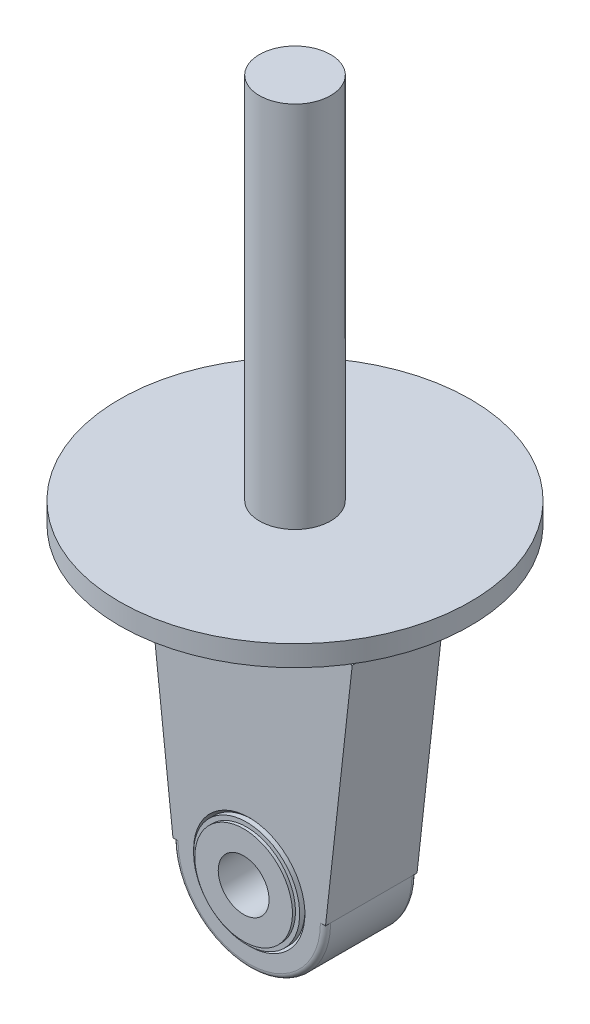
SolidWorks part; units mm, degrees
ref_plane "Front Plane" through (0, 0, 0) normal (0, 0, 1) x (1, 0, 0)
ref_plane "Top Plane" through (0, 0, 0) normal (0, 1, 0) x (1, 0, 0)
ref_plane "Right Plane" through (0, 0, 0) normal (1, 0, 0) x (0, 0, -1)
sketch "Sketch2" plane through (0, 0, 0) normal (0, 1, 0) x (1, 0, 0)
  line L0 (5, 10.1) -> (5, -10.1)
  line L1 (5, 10.1) -> (9.6, 10.1)
  line L2 (9.6, 10.1) -> (9.6, 9.5102)
  line L3 (9.6, 9.5102) -> (10.4331, 9.5102)
  line L4 (10.4331, 9.5102) -> (10.4331, 8.4874)
  line L5 (15, 8) -> (15, -8)
  line L6 (10.4331, 8.4874) -> (10.9456, 9)
  line L7 (0, 9.9454) -> (0, -9.3057) construction
  line L8 (-12.5165, 0) -> (17.2038, 0) construction
  line L9 (10.9456, 9) -> (14, 9)
  line L10 (10.9456, -9) -> (14, -9)
  line L11 (10.4331, -8.4874) -> (10.9456, -9)
  line L13 (10.4331, -9.5102) -> (10.4331, -8.4874)
  line L14 (9.6, -9.5102) -> (10.4331, -9.5102)
  line L15 (9.6, -10.1) -> (9.6, -9.5102)
  line L16 (5, -10.1) -> (9.6, -10.1)
  arc A0 (14, -9) -> (15, -8) centre (14, -8) ccw
  arc A1 (14, 9) -> (15, 8) centre (14, 8) cw
  point P2 (5, 0)
  point P19 (15, -9)
  point P25 (15, 9)
  dimension "D7" = 1
  dimension "D1" = 5
  dimension "D2" = 20.2
  dimension "D3" = 45
  dimension "D4" = 19.2
  dimension "D5" = 18
  dimension "D6" = 15
revolve "Revolve1" add sketch "Sketch2"
sketch "Sketch3" plane through (0, 0, 0) normal (0, 0, 1) x (1, 0, 0)
  line L0 (0, 37.968) -> (0, 0) construction
  line L1 (-20.25, 47) -> (-15, 0)
  line L2 (-15, 0) -> (-10.9456, 0)
  line L3 (-20.25, 47) -> (20.25, 47)
  line L4 (15, 0) -> (10.9456, 0)
  line L5 (20.25, 47) -> (15, 0)
  circle A2 centre (0, 0) radius 15 construction
  circle A3 centre (0, 0) radius 10.9456 construction
  arc A4 (-10.9456, 0) -> (10.9456, 0) centre (0, 0) cw
  point P4 (0, 47)
  dimension "D1" = 47
  dimension "D2" = 40.5
extrude "Extrude1" add sketch "Sketch3" along normal up to surface and the other way up to surface up to face at (-14, 0, 9) other way up to face at (-10.9456, 0, -9)
sketch "Sketch7" plane through (0, 0, 0) normal (0, 0, 1) x (1, 0, 0)
  line L0 (0, 0) -> (0, 99.4646) construction
  line L1 (0, 47) -> (20.25, 47)
  line L2 (0, -25.3108) -> (0, 146.4741) construction
  line L3 (-20.25, 47) -> (20.25, 47) construction
  line L4 (20.25, 47) -> (20.25, 53.1008)
  line L5 (20.25, 53.1008) -> (34.5, 56.3624)
  line L6 (34.5, 56.3624) -> (34.5, 60.45)
  line L7 (34.5, 60.45) -> (7, 60.45)
  line L17 (7, 60.45) -> (7, 132.909)
  line L18 (7, 132.909) -> (0, 132.909)
  line L19 (0, 132.909) -> (0, 47)
  dimension "D1" = 60.45
  dimension "D2" = 7
  dimension "D3" = 69
revolve "Revolve2" add sketch "Sketch7" angle 360 about L0
sketch "Sketch8" plane through (0, 0, 0) normal (0, 0, 1) x (1, 0, 0)
  line L0 (-34.2556, 0) -> (36.0744, 0) construction
  line L1 (-34.2556, 280) -> (36.0744, 280) construction
  dimension "D1" = 280
sketch3d "3DSketch2"
  line L0 (0, 0, 10.1) -> (0, 0, -10.1) construction
  line L1 (0, 0, 10.1) -> (0, 0, -10.1) construction
  line L2 (0, 0, 10.1) -> (0, 0, 9.5102) construction
  point P6 (0, 0, 0)
